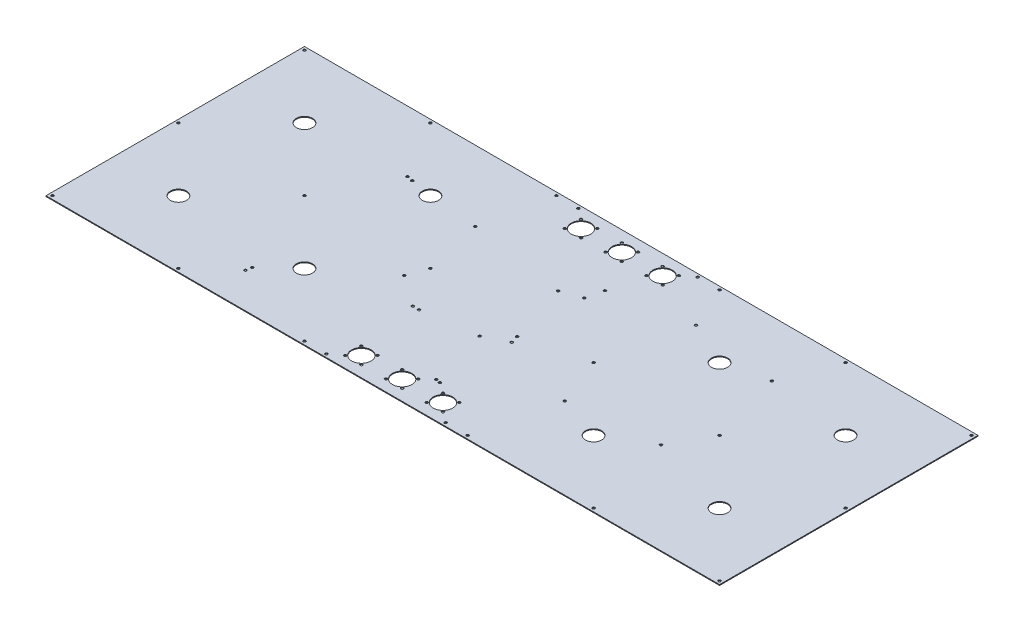
SolidWorks part; units mm, degrees
ref_plane "Front Plane" through (0, 0, 0) normal (0, 0, 1) x (1, 0, 0)
ref_plane "Top Plane" through (0, 0, 0) normal (0, 1, 0) x (1, 0, 0)
ref_plane "Right Plane" through (0, 0, 0) normal (1, 0, 0) x (0, 0, -1)
sketch "main_plate" plane through (0, 0, 0) normal (0, 1, 0) x (1, 0, 0)
  line L1 (-417, 160) -> (417, 160)
  line L2 (-417, 160) -> (-417, -160)
  line L3 (-417, -160) -> (417, -160)
  line L4 (417, 160) -> (417, -160)
  line L5 (-417, 160) -> (417, -160) construction
  line L6 (-417, -160) -> (417, 160) construction
  point P0 (0, 0)
  dimension "D1" = 320
  dimension "D2" = 834
extrude "Boss-Extrude1" add sketch "main_plate" along normal blind 1.016
sketch "main_holes" plane through (0, 1.016, 0) normal (0, 1, 0) x (1, 0, 0)
  line L0 (-417, 160) -> (-417, -160) construction
  line L1 (417, 160) -> (-417, 160) construction
  line L2 (-417, 0) -> (417, 0) construction
  line L3 (417, -160) -> (417, 160) construction
  line L4 (-417, -160) -> (417, -160) construction
  line L5 (0, 160) -> (0, -160) construction
  circle A0 centre (-413, 156) radius 1.6
  circle A6 centre (-257, 156) radius 1.6
  circle A7 centre (-101, 156) radius 1.6
  circle A8 centre (-257, 0) radius 1.6
  circle A9 centre (-101, 0) radius 1.6
  circle A10 centre (-257, -156) radius 1.6
  circle A11 centre (-101, -156) radius 1.6
  circle A12 centre (-413, 0) radius 1.6
  circle A13 centre (-413, -156) radius 1.6
  circle A18 centre (413, -156) radius 1.6
  circle A19 centre (413, 0) radius 1.6
  circle A20 centre (101, -156) radius 1.6
  circle A21 centre (257, -156) radius 1.6
  circle A22 centre (101, 0) radius 1.6
  circle A23 centre (257, 0) radius 1.6
  circle A24 centre (101, 156) radius 1.6
  circle A25 centre (257, 156) radius 1.6
  circle A28 centre (413, 156) radius 1.6
  circle A29 centre (-73.8188, 156) radius 1.6
  circle A31 centre (73.8188, 156) radius 1.6
  circle A32 centre (73.8188, -156) radius 1.6
  circle A33 centre (-73.8188, -156) radius 1.6
  dimension "D3" = 3.2
  dimension "D1" = 4
  dimension "D2" = 4
  dimension "D4" = 3
  dimension "D5" = 3
  dimension "D6" = 73.8188
extrude "Cut-Extrude1" cut sketch "main_holes" against normal through all
sketch "sma" plane through (0, 1.016, 0) normal (0, 1, 0) x (1, 0, 0)
  line L0 (0, 160) -> (0, -160) construction
  line L1 (417, 160) -> (-417, 160) construction
  line L2 (-417, -160) -> (417, -160) construction
  line L3 (-413, 156) -> (-257, 156) construction
  line L7 (-257, 0) -> (-413, 0) construction
  line L8 (-413, 0) -> (-413, 156) construction
  line L9 (-257, 156) -> (-257, 0) construction
  circle A0 centre (-335, 78) radius 10
  circle A1 centre (-179, 78) radius 10
  circle A2 centre (-179, -78) radius 10
  circle A3 centre (-335, -78) radius 10
  circle A4 centre (335, 78) radius 10
  circle A5 centre (179, 78) radius 10
  circle A6 centre (335, -78) radius 10
  circle A7 centre (179, -78) radius 10
  point P9 (-413, 78)
  point P10 (-335, 156)
  dimension "D1" = 20
  dimension "D2" = 2
  dimension "D3" = 2
extrude "Cut-Extrude2" cut sketch "sma" against normal through all
sketch "ads9+eval"
sketch_block_instance "Block9-1"
sketch_block "Block9"
sketch_block_instance "Block8-8"
sketch_block "Block8" parameters "D6"=3.2, "D1"=217.932, "D2"=70.358, "D3"=61.468, "D4"=193.04, "D5"=18.796, "D7"=81.28, "D8"=68.58, "D9"=94.71, "D10"=106.68
sketch_block_instance "Block7-4"
sketch_block "Block7" parameters "D3"=3.2, "D1"=215.9, "D2"=259.71, "D4"=6.48, "D5"=7.24, "D6"=111, "D7"=103.38, "D8"=18.04, "D9"=12.3976, "D10"=37.52, "D11"=11.13, "D12"=13.84, "D13"=110.43, "D14"=101.73, "D15"=7.74, "D16"=6.47, "D17"=37.51, "D18"=13.68, "D19"=8.76, "D20"=15.4, "D21"=8.22, "D22"=100.94, "D23"=7.02, "D24"=8.34, "D25"=18.41, "D26"=36.31, "D27"=27.78, "D28"=7.02, "D29"=8.22, "D30"=9.18, "D31"=73.31, "D32"=73.31, "D33"=82.56, "D34"=105.32, "D35"=95.85
extrude "selective_holes" [suppressed] cut sketch "ads9+eval" against normal through all
sketch "ads9+eval_2" plane through (0, 1.016, 1.016) normal (0, 1, 0) x (1, 0, 0)
  point P0 (94.7943, -70.2336)
  line B0 (10.848, 23.305) -> (247.576, 23.178) construction
  line B1 (29.644, 119.698) -> (247.576, 119.698) construction
  line B2 (29.644, 119.698) -> (29.644, 58.484) construction
  line B3 (29.644, -73.342) -> (247.576, -73.342) construction
  line B4 (247.576, 119.698) -> (247.576, -73.342) construction
  line B5 (29.644, 119.698) -> (247.576, -73.342) construction
  line B6 (29.644, -73.342) -> (247.576, 119.698) construction
  line B7 (10.848, 58.484) -> (29.644, 58.484) construction
  line B8 (10.848, 58.484) -> (10.848, -11.874) construction
  line B9 (10.848, -11.874) -> (29.644, -11.874) construction
  line B10 (29.644, -73.342) -> (29.644, -11.874) construction
  circle B11 centre (124.354, 104.5241) radius 1.6
  circle B12 centre (231.034, 91.7669) radius 1.6
  circle B13 centre (230.9604, -45.3931) radius 1.6
  circle B14 centre (124.2668, -58.0358) radius 1.6
  line B15 (-220.0456, 92.198) -> (39.6644, 92.198) construction
  line B16 (-220.0456, 92.198) -> (-220.0456, -123.702) construction
  line B17 (-220.0456, -123.702) -> (39.6644, -123.702) construction
  line B18 (39.6644, 92.198) -> (39.6644, -123.702) construction
  line B19 (-220.0456, 92.198) -> (39.6644, -123.702) construction
  line B20 (-220.0456, -123.702) -> (39.6644, 92.198) construction
  circle B21 centre (-213.5656, 85.178) radius 1.6
  circle B22 centre (-206.3256, 83.858) radius 1.6
  circle B23 centre (-212.3056, -108.302) radius 1.6
  circle B24 centre (-213.5756, -115.482) radius 1.6
  circle B25 centre (-71.3356, -50.392) radius 1.6
  circle B26 centre (-63.7156, -50.392) radius 1.6
  circle B27 centre (2.1444, -41.142) radius 1.6
  circle B28 centre (-109.6156, -22.762) radius 1.6
  circle B29 centre (28.5344, -27.852) radius 1.6
  circle B30 centre (25.8244, -18.382) radius 1.6
  circle B31 centre (21.6244, -114.522) radius 1.6
  circle B32 centre (27.2668, -115.482) radius 1.6
  circle B33 centre (2.1544, 55.888) radius 1.6
  circle B34 centre (25.9844, 64.418) radius 1.6
  circle B35 centre (30.9044, 85.178) radius 1.6
  circle B36 centre (-118.3156, 73.788) radius 1.6
  dimension "D1" = 27.5
  dimension "D2" = 97
  dimension "D3" = 100.3781
sketch_block_instance "Block8-9"
sketch_block_instance "Block7-5"
extrude "full_holes" cut sketch "ads9+eval_2" against normal through all
sketch "fan" plane through (0, 1.016, -2.032) normal (0, -1, 0) x (1, 0, 0)
  line L0 (417, -157.968) -> (-417, -157.968) construction
  line L1 (-417, 162.032) -> (417, 162.032) construction
  circle B0 centre (-10, -123.968) radius 1.6
  circle B1 centre (10, -123.968) radius 1.6
  circle B2 centre (10, -143.968) radius 1.6
  circle B3 centre (-10, -143.968) radius 1.6
  circle B4 centre (0, -133.968) radius 12
  circle B5 centre (-60.5, -123.968) radius 1.6
  circle B6 centre (-40.5, -123.968) radius 1.6
  circle B7 centre (-40.5, -143.968) radius 1.6
  circle B8 centre (-60.5, -143.968) radius 1.6
  circle B9 centre (-50.5, -133.968) radius 12
  circle B10 centre (40.5, -123.968) radius 1.6
  circle B11 centre (60.5, -123.968) radius 1.6
  circle B12 centre (60.5, -143.968) radius 1.6
  circle B13 centre (40.5, -143.968) radius 1.6
  circle B14 centre (50.5, -133.968) radius 12
  circle B15 centre (-10, -144.984) radius 1.6
  circle B16 centre (10, -144.984) radius 1.6
  circle B17 centre (10, -164.984) radius 1.6
  circle B18 centre (-10, -164.984) radius 1.6
  circle B19 centre (0, -154.984) radius 12
  circle B20 centre (-10, 148.032) radius 1.6
  circle B21 centre (10, 148.032) radius 1.6
  circle B22 centre (10, 128.032) radius 1.6
  circle B23 centre (-10, 128.032) radius 1.6
  circle B24 centre (0, 138.032) radius 12
  circle B25 centre (-60.5, 148.032) radius 1.6
  circle B26 centre (-40.5, 148.032) radius 1.6
  circle B27 centre (-40.5, 128.032) radius 1.6
  circle B28 centre (-60.5, 128.032) radius 1.6
  circle B29 centre (-50.5, 138.032) radius 12
  circle B30 centre (40.5, 148.032) radius 1.6
  circle B31 centre (60.5, 148.032) radius 1.6
  circle B32 centre (60.5, 128.032) radius 1.6
  circle B33 centre (40.5, 128.032) radius 1.6
  circle B34 centre (50.5, 138.032) radius 12
  dimension "D1" = 24
  dimension "D2" = 24
sketch_block_instance "Block13-1"
sketch_block "Block13"
sketch_block_instance "Block2-13"
sketch_block "Block2" parameters "D1"=3.2, "D2"=24, "D3"=10, "D4"=10, "D5"=10, "D6"=10
sketch_block_instance "Block2-14"
sketch_block_instance "Block2-15"
sketch_block_instance "Block2-16"
sketch_block_instance "Block13-2"
extrude "Cut-Extrude4" cut sketch "fan" along normal through all
